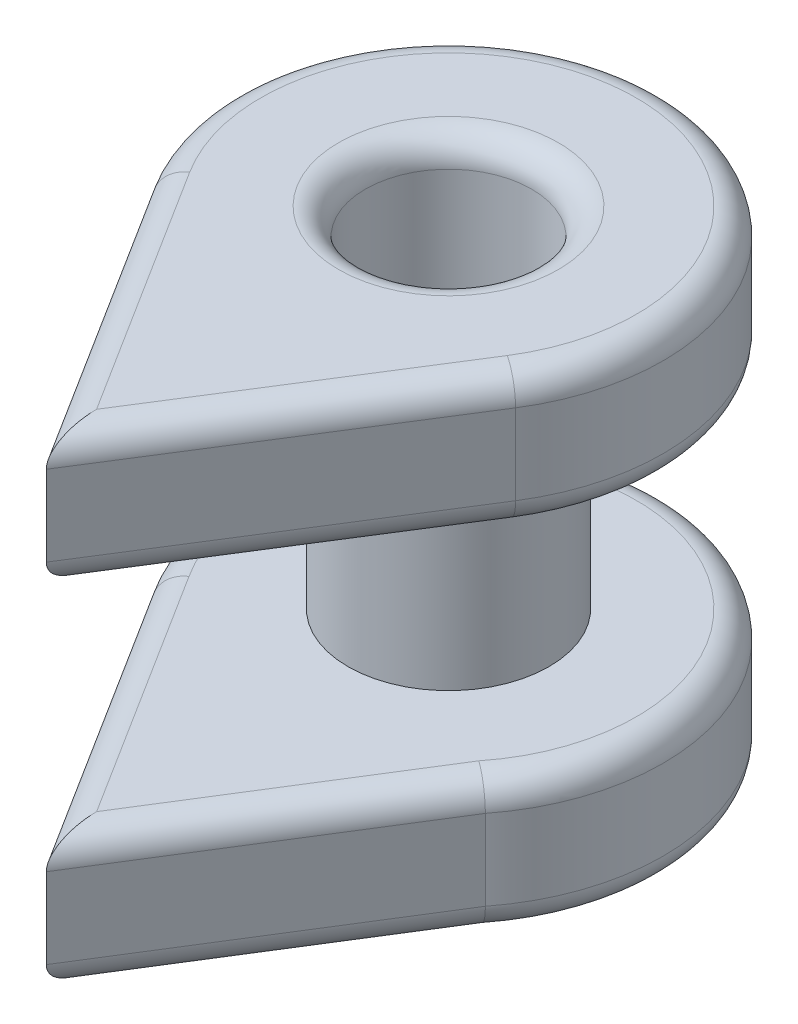
SolidWorks part; units mm, degrees
ref_plane "Front Plane" through (0, 0, 0) normal (0, 0, 1) x (1, 0, 0)
ref_plane "Top Plane" through (0, 0, 0) normal (0, 1, 0) x (1, 0, 0)
ref_plane "Right Plane" through (0, 0, 0) normal (1, 0, 0) x (0, 0, -1)
sketch "Sketch1" plane through (0, 0, 0) normal (0, 1, 0) x (1, 0, 0)
  circle A0 centre (0, 0) radius 3.1
  circle A1 centre (0, 0) radius 3.75
extrude "Boss-Extrude1" add sketch "Sketch1" along normal blind 8
sketch "Sketch2" plane through (0, 8, 0) normal (0, 1, 0) x (1, 0, 0)
  line L0 (0, 0) -> (0, -3.1)
  line L1 (0, -15) -> (-6.7672, -4.2667)
  line L2 (0, -15) -> (6.7672, -4.2667)
  arc A0 (6.7672, -4.2667) -> (-6.7672, -4.2667) centre (0, 0) ccw
  circle A1 centre (0, 0) radius 3.1
  circle M6 centre (0, 0) radius 3.75
  circle M7 centre (0, 0) radius 3.1
extrude "Boss-Extrude4" add sketch "Sketch2" along normal blind 5 contours L2 A0 L1 M6 | M6 M7 region at (-3.1466, 8, 9.4839) region at (-3.6439, 8, 0)
sketch "Sketch3" plane through (0, 0, 0) normal (0, -1, 0) x (1, 0, 0)
  line L1 (0, 15) -> (6.3012, 4.9289)
  line L2 (0, 15) -> (-6.721, 4.3391)
  arc A0 (-6.721, 4.3391) -> (6.3012, 4.9289) centre (0, 0) ccw
  circle A1 centre (0, 0) radius 3.1
extrude "Boss-Extrude5" add sketch "Sketch3" along normal blind 5
fillet "Fillet2" radius 1 3 edges at (-3.3836, 13, 9.6333) (3.3836, 13, 9.6333) (0, 13, -8)
fillet "Fillet3" radius 1 3 edges at (3.1506, -5, 9.9645) (-3.3605, -5, 9.6696) (0.362, -5, -7.9918)
fillet "Fillet4" radius 1 6 edges at (3.1506, 0, 9.9645) (0.362, 0, -7.9918) (-3.3605, 0, 9.6696) (3.3836, 8, 9.6333) (0, 8, -8) (-3.3836, 8, 9.6333)
fillet "Fillet5" radius 1 1 edges at (0, 13, 3.1)
fillet "Fillet6" radius 1 1 edges at (0, -5, -3.1)
